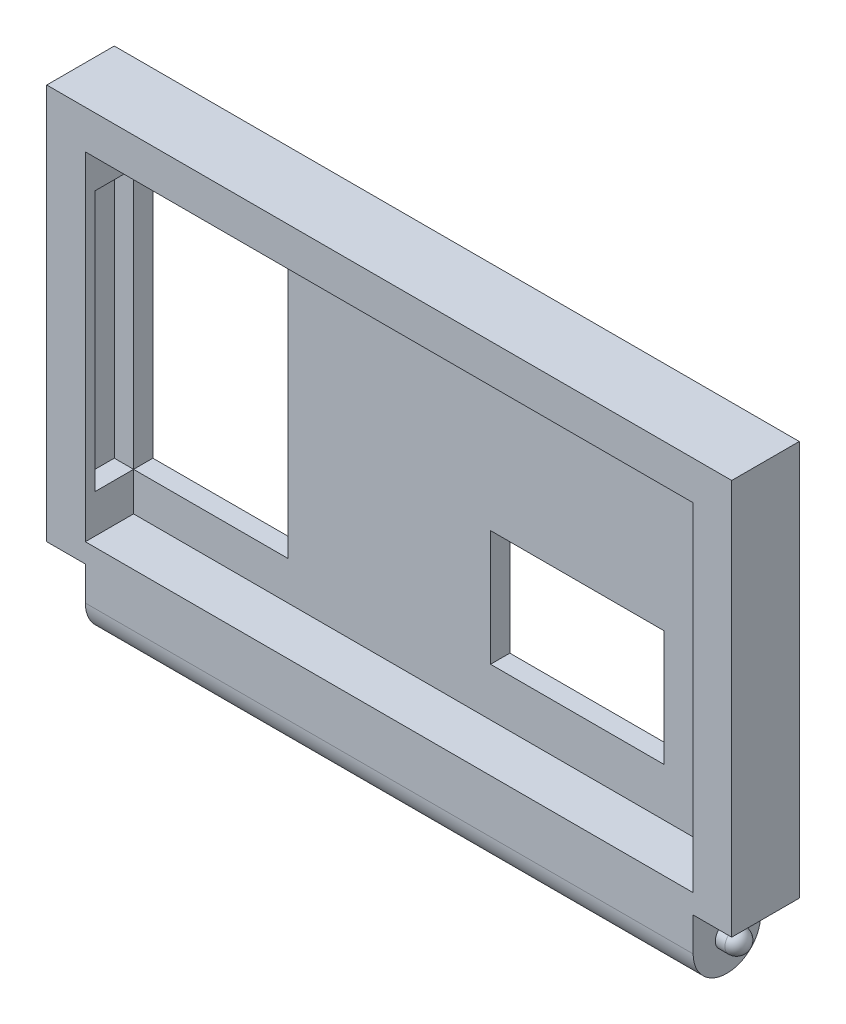
SolidWorks part; units mm, degrees
ref_plane "前视基准面" through (0, 0, 0) normal (0, 0, 1) x (1, 0, 0)
ref_plane "上视基准面" through (0, 0, 0) normal (0, 1, 0) x (1, 0, 0)
ref_plane "右视基准面" through (0, 0, 0) normal (1, 0, 0) x (0, 0, -1)
sketch "草图1" plane through (0, 0, 0) normal (0, 0, 1) x (1, 0, 0)
  line L1 (-17.75, 12) -> (17.75, 12)
  line L2 (-17.75, 12) -> (-17.75, -12)
  line L3 (-17.75, -12) -> (17.75, -12)
  line L4 (17.75, 12) -> (17.75, -12)
  line L5 (-17.75, 12) -> (17.75, -12) construction
  line L6 (-17.75, -12) -> (17.75, 12) construction
  point P0 (0, 0)
  dimension "D1" = 35.5
  dimension "D2" = 24
extrude "凸台-拉伸1" add sketch "草图1" along normal blind 3.5
sketch "草图2" plane through (0, 0, 3.5) normal (0, 0, 1) x (1, 0, 0)
  line L0 (-17.75, 12) -> (-17.75, -12) construction
  line L1 (-15.75, 10) -> (15.75, 10)
  line L2 (-15.75, 10) -> (-15.75, -7.5)
  line L3 (-15.75, -7.5) -> (15.75, -7.5)
  line L4 (15.75, 10) -> (15.75, -7.5)
  line L5 (17.75, -12) -> (17.75, 12) construction
  line L8 (17.75, 12) -> (-17.75, 12) construction
  dimension "D1" = 2
  dimension "D2" = 2
  dimension "D3" = 2
  dimension "D4" = 17.5
extrude "切除-拉伸1" cut sketch "草图2" against normal blind 2.5
sketch "草图12" plane through (-17.75, 0, 0) normal (-1, 0, 0) x (0, 0, 1)
  line L5 (3.5, 12) -> (3.5, -12) construction
  line L6 (0, -12) -> (3.5, -12)
  line L7 (0, -12) -> (0, -8.5)
  line L8 (0, -8.5) -> (3.5, -8.5)
  line L9 (3.5, -12) -> (3.5, -8.5)
  dimension "D1" = 3.5
  dimension "D2" = 3.5
extrude "切除-拉伸9" cut sketch "草图12" against normal blind 2
sketch "草图13" plane through (17.75, 0, 0) normal (1, 0, 0) x (0, 0, -1)
  line L0 (0, -12) -> (0, 12) construction
  line L1 (-3.5, -12) -> (0, -12)
  line L2 (-3.5, -12) -> (-3.5, -8.5)
  line L3 (-3.5, -8.5) -> (0, -8.5)
  line L4 (0, -12) -> (0, -8.5)
  dimension "D1" = 3.5
  dimension "D2" = 3.5
extrude "切除-拉伸10" cut sketch "草图13" against normal blind 2
sketch "草图14" plane through (0, 0, 1) normal (0, 0, 1) x (1, 0, 0)
  line L1 (-15.75, 8) -> (-7.75, 8)
  line L2 (-15.75, 8) -> (-15.75, -5.5)
  line L3 (-15.75, -5.5) -> (-7.75, -5.5)
  line L4 (-7.75, 8) -> (-7.75, -5.5)
  line L7 (15.75, 10) -> (-15.75, 10) construction
  line L8 (-15.75, -7.5) -> (15.75, -7.5) construction
  dimension "D1" = 8
  dimension "D2" = 2
  dimension "D3" = 2
extrude "切除-拉伸11" cut sketch "草图14" against normal blind 2
sketch "草图18" plane through (-15.75, 0, 0) normal (1, 0, 0) x (0, 0, -1)
  line L0 (-3.5, 10) -> (-3.5, -7.5) construction
  line L1 (-1, 8) -> (-3, 8)
  line L2 (-1, 8) -> (-1, -5.5)
  line L3 (-1, -5.5) -> (-3, -5.5)
  line L4 (-3, 8) -> (-3, -5.5)
  dimension "D1" = 2
  dimension "D2" = 0.5
  dimension "D3" = 13.5
extrude "切除-拉伸12" cut sketch "草图18" against normal blind 1
sketch "草图19" plane through (0, 0, 1) normal (0, 0, 1) x (1, 0, 0)
  line L0 (-15.75, -7.5) -> (15.75, -7.5) construction
  line L1 (2.75, 1) -> (11.75, 1)
  line L2 (2.75, 1) -> (2.75, -5)
  line L3 (2.75, -5) -> (11.75, -5)
  line L4 (11.75, 1) -> (11.75, -5)
  line L5 (15.75, -7.5) -> (15.75, 10) construction
  dimension "D1" = 6
  dimension "D2" = 2.5
  dimension "D3" = 9
  dimension "D4" = 4
extrude "切除-拉伸13" cut sketch "草图19" against normal blind 2
sketch "草图20" plane through (-15.75, 0, 0) normal (-1, 0, 0) x (0, 0, 1)
  line L0 (3.5, -12) -> (3.5, -8.5) construction
  line L3 (0, -12) -> (3.5, -12) construction
  circle A0 centre (1.75, -10.25) radius 0.6
  dimension "D1" = 1.2
  dimension "D3" = 1.75
  dimension "D2" = 1.75
extrude "凸台-拉伸3" add sketch "草图20" along normal blind 0.5
sketch "草图21" plane through (15.75, 0, 0) normal (1, 0, 0) x (0, 0, -1)
  line L0 (0, -12) -> (0, -8.5) construction
  line L2 (0, -8.5) -> (-3.5, -8.5) construction
  circle A0 centre (-1.75, -10.25) radius 0.6
  dimension "D1" = 1.2
  dimension "D2" = 1.75
  dimension "D3" = 1.75
extrude "凸台-拉伸4" add sketch "草图21" along normal blind 0.5
sketch "草图23" plane through (-16.25, 0, 0) normal (-1, 0, 0) x (0, 0, 1)
  line L0 (1.75, -9.65) -> (1.75, -10.85)
  circle A1 centre (1.75, -10.25) radius 0.6 construction
  circle A2 centre (1.75, -10.25) radius 0.6 construction
  arc A3 (1.75, -10.85) -> (1.75, -9.65) centre (1.75, -10.25) ccw
revolve "旋转1" add sketch "草图23" angle 360 about L0
sketch "草图24" plane through (16.25, 0, 0) normal (1, 0, 0) x (0, 0, -1)
  line L0 (-1.3595, -10.7055) -> (-2.1405, -9.7945)
  circle A5 centre (-1.75, -10.25) radius 0.6 construction
  circle A6 centre (-1.75, -10.25) radius 0.6 construction
  arc A7 (-2.1405, -9.7945) -> (-1.3595, -10.7055) centre (-1.75, -10.25) ccw
revolve "旋转2" add sketch "草图24" angle 360 about L0 region at (16.25, -10.4157, 1.9433)
fillet "圆角1" radius 1.75 1 edges at (0, -12, 3.5)
fillet "圆角2" radius 1.75 1 edges at (0, -12, 0)
